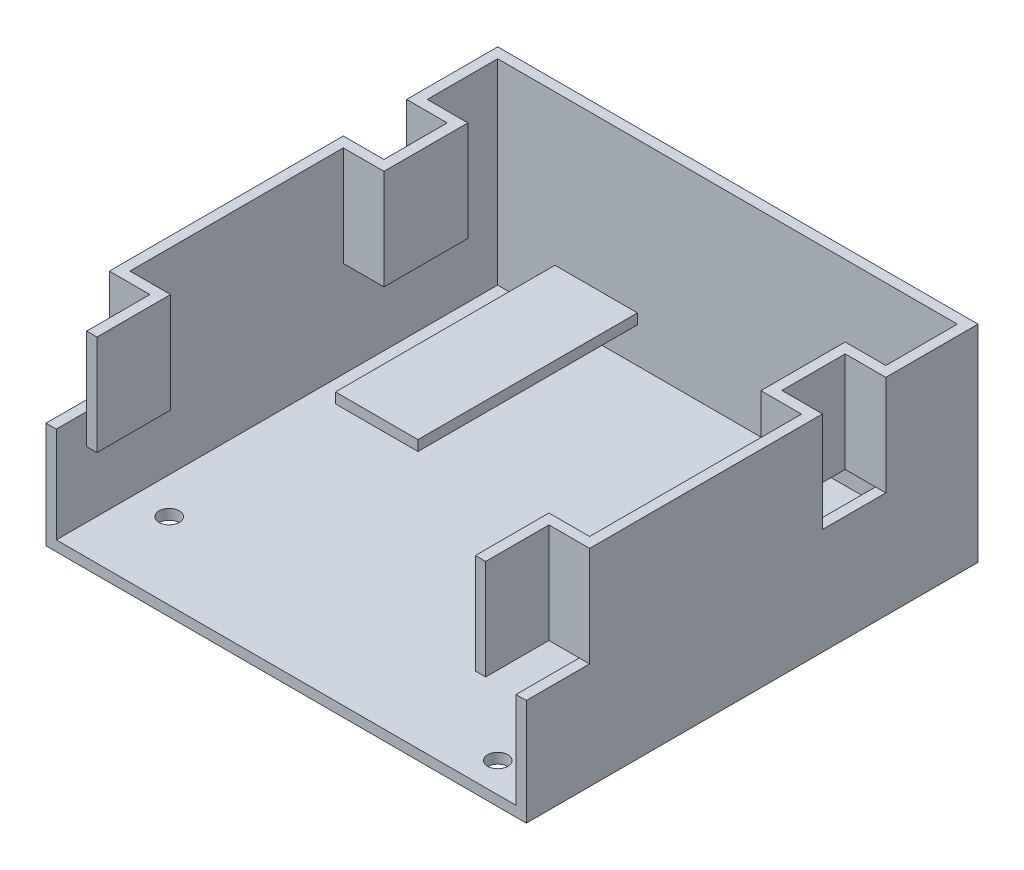
SolidWorks part; units mm, degrees
ref_plane "Front Plane" through (0, 0, 0) normal (0, 0, 1) x (1, 0, 0)
ref_plane "Top Plane" through (0, 0, 0) normal (0, 1, 0) x (1, 0, 0)
ref_plane "Right Plane" through (0, 0, 0) normal (1, 0, 0) x (0, 0, -1)
sketch "Sketch1" plane through (0, 0, 0) normal (0, 1, 0) x (1, 0, 0)
  line L1 (0, 0) -> (89.12, 0)
  line L2 (0, 0) -> (0, 85.57)
  line L3 (0, 85.57) -> (89.12, 85.57)
  line L4 (89.12, 0) -> (89.12, 85.57)
  dimension "D1" = 89.12
  dimension "D2" = 85.57
extrude "Boss-Extrude1" add sketch "Sketch1" along normal blind 2
sketch "Sketch3" plane through (0, 0, 0) normal (0, 0, 1) x (1, 0, 0)
  line L1 (0, 0) -> (-2, 0)
  line L2 (0, 0) -> (0, 30)
  line L3 (0, 30) -> (-2, 30)
  line L4 (-2, 0) -> (-2, 30)
  dimension "D1" = 2
  dimension "D2" = 30
extrude "Boss-Extrude2" add sketch "Sketch3" against normal blind 85.57
sketch "Sketch4" plane through (0, 0, 0) normal (0, 0, 1) x (1, 0, 0)
  line L1 (89.12, 0) -> (91.12, 0)
  line L2 (89.12, 0) -> (89.12, 30)
  line L3 (89.12, 30) -> (91.12, 30)
  line L4 (91.12, 0) -> (91.12, 30)
  dimension "D1" = 30
  dimension "D2" = 2
extrude "Boss-Extrude3" add sketch "Sketch4" against normal blind 85.57
sketch "Sketch5" plane through (0, 0, 0) normal (0, 1, 0) x (1, 0, 0)
  line L1 (-2, 85.57) -> (91.12, 85.57)
  line L2 (-2, 85.57) -> (-2, 87.57)
  line L3 (-2, 87.57) -> (91.12, 87.57)
  line L4 (91.12, 85.57) -> (91.12, 87.57)
  dimension "D1" = 2
extrude "Boss-Extrude4" add sketch "Sketch5" along normal blind 30
sketch "Sketch6" plane through (0, 0, 0) normal (0, 1, 0) x (1, 0, 0)
  line L0 (89.12, 0) -> (89.12, 5.755) construction
  line L1 (89.12, 0) -> (89.12, 85.57) construction
  line L2 (89.12, 5.755) -> (79.835, 5.755) construction
  line L3 (79.835, 5.755) -> (79.835, 0) construction
  line L4 (0, 0) -> (89.12, 0) construction
  circle A0 centre (79.835, 5.755) radius 1.96
  dimension "D3" = 3.92
extrude "Cut-Extrude2" cut sketch "Sketch6" along normal blind 30
sketch "Sketch7" plane through (0, 2, 0) normal (0, 1, 0) x (1, 0, 0)
  line L0 (89.12, 85.57) -> (82.285, 85.57) construction
  line L1 (0, 85.57) -> (89.12, 85.57) construction
  line L2 (82.285, 85.57) -> (82.285, 76.225) construction
  line L3 (82.285, 76.225) -> (89.12, 76.225) construction
  line L4 (89.12, 0) -> (89.12, 85.57) construction
  circle A0 centre (82.285, 76.225) radius 1.96
  dimension "D3" = 3.92
  dimension "D1" = 6.835
extrude "Cut-Extrude3" cut sketch "Sketch7" against normal blind 30
sketch "Sketch8" plane through (0, 0, 0) normal (0, 1, 0) x (1, 0, 0)
  line L0 (0, 85.57) -> (6.985, 85.57) construction
  line L1 (0, 85.57) -> (89.12, 85.57) construction
  line L2 (6.985, 85.57) -> (6.985, 78.28) construction
  line L3 (6.985, 78.28) -> (0, 78.28) construction
  line L4 (0, 85.57) -> (0, 0) construction
  circle A0 centre (6.985, 78.28) radius 1.96
  dimension "D3" = 3.92
extrude "Cut-Extrude4" cut sketch "Sketch8" along normal blind 30
sketch "Sketch9" plane through (0, 2, 0) normal (0, 1, 0) x (1, 0, 0)
  line L0 (0, 0) -> (0, 14.85) construction
  line L1 (0, 85.57) -> (0, 0) construction
  line L2 (0, 14.85) -> (7.035, 14.85) construction
  line L3 (7.035, 14.85) -> (7.035, 0) construction
  line L4 (0, 0) -> (89.12, 0) construction
  circle A0 centre (7.035, 14.85) radius 1.96
  dimension "D3" = 3.92
  dimension "D1" = 14.85
extrude "Cut-Extrude5" cut sketch "Sketch9" against normal blind 30
sketch "Sketch10" plane through (89.12, 0, 0) normal (-1, 0, 0) x (0, 0, 1)
  line L0 (0, 2) -> (0, 20.6) construction
  line L1 (0, 30) -> (0, 2) construction
  line L2 (0, 20.6) -> (-32.6241, 20.6) construction
  line L3 (-32.6241, 20.6) -> (-32.6241, 2) construction
  line L4 (0, 2) -> (-85.57, 2) construction
  line L5 (-32.6241, 20.6) -> (-32.6241, 30) construction
  line L6 (-85.57, 30) -> (0, 30) construction
  dimension "D1" = 18.6
sketch "Sketch11" plane through (0, 30, 0) normal (0, 1, 0) x (1, 0, 0)
  line L1 (89.12, 0) -> (83.24, 0)
  line L2 (89.12, 0) -> (89.12, 12.27)
  line L3 (89.12, 12.27) -> (83.24, 12.27)
  line L4 (83.24, 0) -> (83.24, 12.27)
  line L5 (83.24, 0) -> (81.24, 0)
  line L6 (83.24, 0) -> (83.24, 12.27)
  line L7 (83.24, 12.27) -> (81.24, 12.27)
  line L8 (81.24, 0) -> (81.24, 12.27)
  line L9 (81.24, 12.27) -> (89.12, 12.27)
  line L10 (81.24, 12.27) -> (81.24, 14.27)
  line L11 (81.24, 14.27) -> (89.12, 14.27)
  line L12 (89.12, 12.27) -> (89.12, 14.27)
  line M8 (89.12, 85.57) -> (89.12, 0)
  dimension "D1" = 5.88
  dimension "D2" = 12.27
  dimension "D3" = 2
  dimension "D4" = 2
extrude "Boss-Extrude5" add sketch "Sketch11" against normal blind 9.4 contours L11 L10 L7 L3 M8 | L8 L5 L4 L7 region at (82.24, 30, -6.135) region at (85.18, 30, -13.27)
sketch "Sketch12" plane through (0, 30, 0) normal (0, 1, 0) x (1, 0, 0)
  line L1 (89.12, 12.27) -> (91.12, 12.27)
  line L2 (89.12, 12.27) -> (89.12, 0)
  line L3 (89.12, 0) -> (91.12, 0)
  line L4 (91.12, 12.27) -> (91.12, 0)
extrude "Cut-Extrude6" cut sketch "Sketch12" against normal blind 9.4
sketch "Sketch13" plane through (0, 30, 0) normal (0, 1, 0) x (1, 0, 0)
  line L0 (89.12, 85.57) -> (89.12, 57.43) construction
  line L1 (89.12, 85.57) -> (89.12, 14.27) construction
  line L3 (89.12, 57.43) -> (83.24, 57.43)
  line L4 (89.12, 57.43) -> (89.12, 69.7)
  line L5 (89.12, 69.7) -> (83.24, 69.7)
  line L6 (83.24, 57.43) -> (83.24, 69.7)
  line L7 (83.24, 69.7) -> (81.24, 69.7)
  line L8 (83.24, 69.7) -> (83.24, 57.43)
  line L9 (83.24, 57.43) -> (81.24, 57.43)
  line L10 (81.24, 69.7) -> (81.24, 57.43)
  line L11 (81.24, 57.43) -> (89.12, 57.43)
  line L12 (81.24, 57.43) -> (81.24, 55.3598)
  line L13 (81.24, 55.3598) -> (89.12, 55.3598)
  line L14 (89.12, 57.43) -> (89.12, 55.3598)
  line L15 (81.24, 69.7) -> (89.12, 69.7)
  line L16 (81.24, 69.7) -> (81.24, 71.7)
  line L17 (81.24, 71.7) -> (89.12, 71.7)
  line L18 (89.12, 69.7) -> (89.12, 71.7)
  line M25 (89.12, 85.57) -> (89.12, 14.27)
  dimension "D1" = 28.14
  dimension "D2" = 12.27
  dimension "D3" = 5.88
  dimension "D4" = 2
  dimension "D5" = 2.0702
  dimension "D6" = 2
extrude "Boss-Extrude6" add sketch "Sketch13" against normal blind 9.4 contours L17 L16 L7 L5 M25 | L7 L10 L9 L6 | L12 L13 L3 L9 M25 region at (85.18, 30, -56.3949) region at (82.24, 30, -63.565) region at (85.18, 30, -70.7)
sketch "Sketch14" plane through (0, 30, 0) normal (0, 1, 0) x (1, 0, 0)
  line L0 (91.12, 87.57) -> (91.12, 12.27) construction
  line L1 (89.12, 69.7) -> (91.12, 69.7)
  line L2 (89.12, 69.7) -> (89.12, 57.43)
  line L3 (89.12, 57.43) -> (91.12, 57.43)
  line L4 (91.12, 69.7) -> (91.12, 57.43)
extrude "Cut-Extrude7" cut sketch "Sketch14" against normal blind 9.4
sketch "Sketch15" plane through (0, 30, 0) normal (0, 1, 0) x (1, 0, 0)
  line L0 (0, 85.57) -> (0, 57.64) construction
  line L1 (0, 85.57) -> (0, 0) construction
  line L3 (0, 57.64) -> (5.88, 57.64)
  line L4 (0, 57.64) -> (0, 69.91)
  line L5 (0, 69.91) -> (5.88, 69.91)
  line L6 (5.88, 57.64) -> (5.88, 69.91)
  line L7 (5.88, 69.91) -> (7.88, 69.91)
  line L8 (5.88, 69.91) -> (5.88, 57.64)
  line L9 (5.88, 57.64) -> (7.88, 57.64)
  line L10 (7.88, 69.91) -> (7.88, 57.64)
  line L11 (0, 57.64) -> (7.88, 57.64)
  line L12 (0, 57.64) -> (0, 55.64)
  line L13 (0, 55.64) -> (7.88, 55.64)
  line L14 (7.88, 57.64) -> (7.88, 55.64)
  line L15 (0, 69.91) -> (7.88, 69.91)
  line L16 (0, 69.91) -> (0, 71.91)
  line L17 (0, 71.91) -> (7.88, 71.91)
  line L18 (7.88, 69.91) -> (7.88, 71.91)
  line M12 (0, 0) -> (0, 85.57)
  dimension "D1" = 27.93
  dimension "D2" = 5.88
  dimension "D3" = 12.27
  dimension "D4" = 2
  dimension "D5" = 2
  dimension "D6" = 2
extrude "Boss-Extrude7" add sketch "Sketch15" against normal blind 9.4 contours L7 L18 L17 L5 M12 | L10 L7 L6 L9 | L14 L9 L3 L13 M12 region at (3.94, 30, -56.64) region at (6.88, 30, -63.775) region at (3.94, 30, -70.91)
sketch "Sketch16" plane through (0, 30, 0) normal (0, 1, 0) x (1, 0, 0)
  line L0 (-2, 87.57) -> (-2, 0) construction
  line L1 (-2, 69.91) -> (0, 69.91)
  line L2 (-2, 69.91) -> (-2, 57.64)
  line L3 (-2, 57.64) -> (0, 57.64)
  line L4 (0, 69.91) -> (0, 57.64)
extrude "Cut-Extrude8" cut sketch "Sketch16" against normal blind 9.4
sketch "Sketch17" plane through (0, 30, 0) normal (0, 1, 0) x (1, 0, 0)
  line L0 (0, 0) -> (89.12, 0) construction
  line L1 (0, 0) -> (5.88, 0)
  line L2 (0, 0) -> (0, 12.27)
  line L3 (0, 12.27) -> (5.88, 12.27)
  line L4 (5.88, 0) -> (5.88, 12.27)
  line L5 (5.88, 12.27) -> (7.88, 12.27)
  line L6 (5.88, 12.27) -> (5.88, 0)
  line L7 (5.88, 0) -> (7.88, 0)
  line L8 (7.88, 12.27) -> (7.88, 0)
  line L9 (0, 55.64) -> (0, 0) construction
  line L10 (7.88, 12.27) -> (0, 12.27)
  line L11 (7.88, 12.27) -> (7.88, 14.27)
  line L12 (7.88, 14.27) -> (0, 14.27)
  line L13 (0, 12.27) -> (0, 14.27)
  line M13 (0, 0) -> (0, 55.64)
  dimension "D1" = 12.27
  dimension "D2" = 5.88
  dimension "D3" = 2
  dimension "D4" = 2
extrude "Boss-Extrude8" add sketch "Sketch17" against normal blind 9.4 contours L11 L12 L3 L5 M13 | L8 L5 L4 L7 region at (6.88, 30, -6.135) region at (3.94, 30, -13.27)
sketch "Sketch18" plane through (0, 30, 0) normal (0, 1, 0) x (1, 0, 0)
  line L0 (-2, 57.64) -> (-2, 0) construction
  line L1 (0, 0) -> (-2, 0)
  line L2 (0, 0) -> (0, 12.27)
  line L3 (0, 12.27) -> (-2, 12.27)
  line L4 (-2, 0) -> (-2, 12.27)
extrude "Cut-Extrude9" cut sketch "Sketch18" against normal blind 9.4
sketch "Sketch19" plane through (0, 30, 0) normal (0, 1, 0) x (1, 0, 0)
  line L0 (83.24, 0) -> (81.24, 0)
  line L1 (81.24, 0) -> (81.24, 14.27)
  line L2 (81.24, 0) -> (81.24, 14.27) construction
  line L3 (81.24, 14.27) -> (89.12, 14.27)
  line L4 (89.12, 14.27) -> (89.12, 55.3598)
  line L5 (89.12, 55.3598) -> (81.24, 55.3598)
  line L6 (81.24, 55.3598) -> (81.24, 71.7)
  line L7 (81.24, 71.7) -> (89.12, 71.7)
  line L8 (89.12, 71.7) -> (89.12, 85.57)
  line L9 (89.12, 85.57) -> (0, 85.57)
  line L10 (0, 85.57) -> (0, 71.91)
  line L11 (0, 71.91) -> (7.88, 71.91)
  line L12 (7.88, 71.91) -> (7.88, 55.64)
  line L13 (7.88, 55.64) -> (0, 55.64)
  line L14 (0, 55.64) -> (0, 14.27)
  line L15 (0, 14.27) -> (7.88, 14.27)
  line L16 (7.88, 14.27) -> (7.88, 0)
  line L17 (7.88, 0) -> (5.88, 0)
  line L18 (5.88, 0) -> (5.88, 12.27)
  line L19 (5.88, 12.27) -> (-2, 12.27)
  line L20 (-2, 12.27) -> (-2, 57.64)
  line L21 (-2, 57.64) -> (5.88, 57.64)
  line L22 (5.88, 57.64) -> (5.88, 69.91)
  line L23 (5.88, 69.91) -> (-2, 69.91)
  line L24 (-2, 69.91) -> (-2, 87.57)
  line L25 (-2, 87.57) -> (91.12, 87.57)
  line L26 (91.12, 87.57) -> (91.12, 69.7)
  line L27 (91.12, 69.7) -> (83.24, 69.7)
  line L28 (83.24, 69.7) -> (83.24, 57.43)
  line L29 (83.24, 57.43) -> (91.12, 57.43)
  line L30 (91.12, 57.43) -> (91.12, 12.27)
  line L31 (91.12, 12.27) -> (83.24, 12.27)
  line L32 (83.24, 12.27) -> (83.24, 0)
extrude "Boss-Extrude9" add sketch "Sketch19" along normal blind 10
sketch "Sketch20" plane through (0, 2, 0) normal (0, 1, 0) x (1, 0, 0)
  line L0 (0, 85.57) -> (27.1, 85.57) construction
  line L1 (89.12, 85.57) -> (0, 85.57) construction
  line L2 (27.1, 85.57) -> (27.1, 43.02) construction
  line L3 (27.1, 43.02) -> (11.1, 43.02) construction
  line L4 (11.1, 43.02) -> (11.1, 85.57) construction
  line L6 (11.1, 85.57) -> (27.1, 85.57)
  line L7 (11.1, 85.57) -> (11.1, 43.02)
  line L8 (11.1, 43.02) -> (27.1, 43.02)
  line L9 (27.1, 85.57) -> (27.1, 43.02)
  dimension "D1" = 42.55
  dimension "D2" = 27.1
  dimension "D3" = 16
extrude "Boss-Extrude10" add sketch "Sketch20" along normal blind 8.88
sketch "Sketch21" plane through (0, 0, -43.02) normal (0, 0, 1) x (1, 0, 0)
  line L0 (27.1, 10.88) -> (27.1, 2) construction
  line L1 (11.1, 10.88) -> (27.1, 10.88)
  line L2 (11.1, 10.88) -> (11.1, 8.88)
  line L3 (11.1, 8.88) -> (27.1, 8.88)
  line L4 (27.1, 10.88) -> (27.1, 8.88)
  line L6 (11.1, 8.88) -> (27.1, 8.88)
  line L7 (11.1, 8.88) -> (11.1, 2)
  line L8 (11.1, 2) -> (27.1, 2)
  line L9 (27.1, 8.88) -> (27.1, 2)
  line M2 (11.1, 2) -> (27.1, 2)
  line M3 (27.1, 2) -> (27.1, 10.88)
  line M5 (11.1, 10.88) -> (11.1, 2)
  dimension "D1" = 2
extrude "Cut-Extrude10" cut sketch "Sketch21" against normal blind 42.55 contours L3 M5 M2 M3 region at (19.1, 5.44, -43.02)
equation "\"tol1\"= 0.1cm"
equation "\"D1@Sketch1\"=8.812cm +\"tol1\""
equation "\"D2@Sketch1\"=8.457cm +\"tol1\""
equation "\"D1@Boss-Extrude2\"=8.457 +\"tol1\""
equation "\"D1@Boss-Extrude3\"=8.457 +\"tol1\""
equation "\"D1@Sketch6\"=0.5255 + \"tol2\""
equation "\"hole\"= 0.392cm"
equation "\"D3@Sketch6\"=\"hole\""
equation "\"tol2\"= \"tol1\" / 2"
equation "\"D2@Sketch6\"=0.8785 + \"tol2\""
equation "\"D2@Sketch9\"=0.6535 + \"tol2\""
equation "\"D3@Sketch9\"=\"hole\""
equation "\"D1@Sketch9\"=1.435 + \"tol2\""
equation "\"D2@Sketch8\"=0.6485 + \"tol2\""
equation "\"D1@Sketch8\"=0.679 + \"tol2\""
equation "\"D3@Sketch8\"=\"hole\""
equation "\"D3@Sketch7\"=\"hole\""
equation "\"D2@Sketch7\"=0.8845 + \"tol2\""
equation "\"D1@Sketch7\"=0.6335 + \"tol2\""
equation "\"heightTol\"= 0.5cm"
equation "\"D1@Sketch10\"=1.36 + \"heightTol\""
equation "\"D2@Sketch20\"=2.61 + \"tol1\""
equation "\"D1@Boss-Extrude10\"=0.588 + \"tol1\" +0.2"
